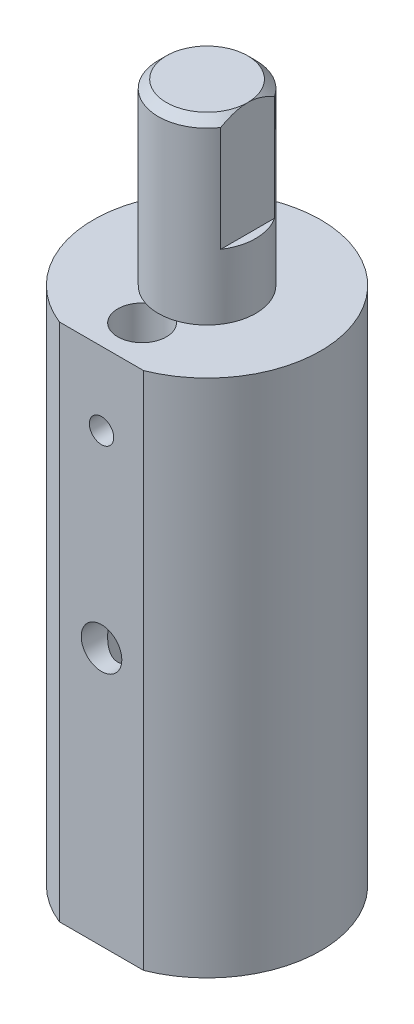
SolidWorks part; units mm, degrees
ref_plane "Front Plane" through (0, 0, 0) normal (0, 0, 1) x (1, 0, 0)
ref_plane "Top Plane" through (0, 0, 0) normal (0, 1, 0) x (1, 0, 0)
ref_plane "Right Plane" through (0, 0, 0) normal (1, 0, 0) x (0, 0, -1)
sketch "Sketch1" plane through (0, 0, 0) normal (0, 1, 0) x (1, 0, 0)
  line L0 (5.1962, -13) -> (-5.1962, -13)
  arc A0 (5.1962, -13) -> (-5.1962, -13) centre (0, 0) ccw
  circle A1 centre (-9, 0) radius 2
  circle A2 centre (9, 0) radius 2
  circle A3 centre (0, 5) radius 6
  circle A4 centre (0, -8) radius 3
  dimension "D1" = 28
  dimension "D2" = 4
  dimension "D3" = 4
  dimension "D4" = 6
  dimension "D5" = 12
  dimension "D6" = 5
  dimension "D7" = 9
  dimension "D8" = 9
  dimension "D9" = 8
  dimension "D10" = 13
extrude "Boss-Extrude1" add sketch "Sketch1" along normal blind 14
sketch "Sketch2" plane through (0, 14, 0) normal (0, 1, 0) x (1, 0, 0)
  line L1 (-5.1962, -13) -> (5.1962, -13)
  line L2 (-5.1962, -13) -> (5.1962, -13)
  circle A0 centre (0, 5) radius 6 construction
  arc A1 (5.1962, -13) -> (-5.1962, -13) centre (0, 0) ccw
  arc A2 (5.1962, -13) -> (-5.1962, -13) centre (0, 0) ccw
  circle A3 centre (0, 5) radius 6
  circle A4 centre (0, -8) radius 3 construction
  circle A5 centre (0, -8) radius 3
  dimension "D1" = 0
extrude "Boss-Extrude2" add sketch "Sketch2" along normal blind 38
sketch "Sketch3" plane through (0, 52, 0) normal (0, 1, 0) x (1, 0, 0)
  line L1 (-5.1962, -13) -> (5.1962, -13)
  line L2 (-5.1962, -13) -> (5.1962, -13)
  circle A0 centre (0, -8) radius 3 construction
  arc A1 (5.1962, -13) -> (-5.1962, -13) centre (0, 0) ccw
  arc A2 (5.1962, -13) -> (-5.1962, -13) centre (0, 0) ccw
  circle A3 centre (0, -8) radius 3
  dimension "D1" = 0
extrude "Boss-Extrude3" add sketch "Sketch3" along normal blind 12
sketch "Sketch4" plane through (0, 64, 0) normal (0, 1, 0) x (1, 0, 0)
  circle A0 centre (0, 0) radius 6
  dimension "D1" = 12
extrude "Boss-Extrude4" add sketch "Sketch4" along normal blind 22
sketch "Sketch5" plane through (0, 86, 0) normal (0, 1, 0) x (1, 0, 0)
  line L0 (5, 3.3166) -> (5, -3.3166)
  circle A0 centre (0, 0) radius 6 construction
  circle A2 centre (0, 0) radius 6
  arc A3 (5, -3.3166) -> (5, 3.3166) centre (0, 0) ccw
  dimension "D1" = 5
  dimension "D2" = 0
extrude "Cut-Extrude1" cut sketch "Sketch5" against normal blind 14
chamfer "Chamfer1" distance 1 angle 45 1 edges at (-6, 86, 0)
sketch "Sketch6" plane through (0, 0, 13) normal (0, 0, 1) x (1, 0, 0)
  circle A1 centre (0, 31.8006) radius 2.5
  dimension "D1" = 5
extrude "Cut-Extrude2" cut sketch "Sketch6" against normal blind 5
sketch "Sketch7" plane through (0, 0, 13) normal (0, 0, 1) x (1, 0, 0)
  line L1 (-5.1962, 64) -> (5.1962, 64) construction
  circle A0 centre (0, 55) radius 1.5
  dimension "D1" = 3
  dimension "D2" = 9
extrude "Cut-Extrude3" cut sketch "Sketch7" against normal blind 15
